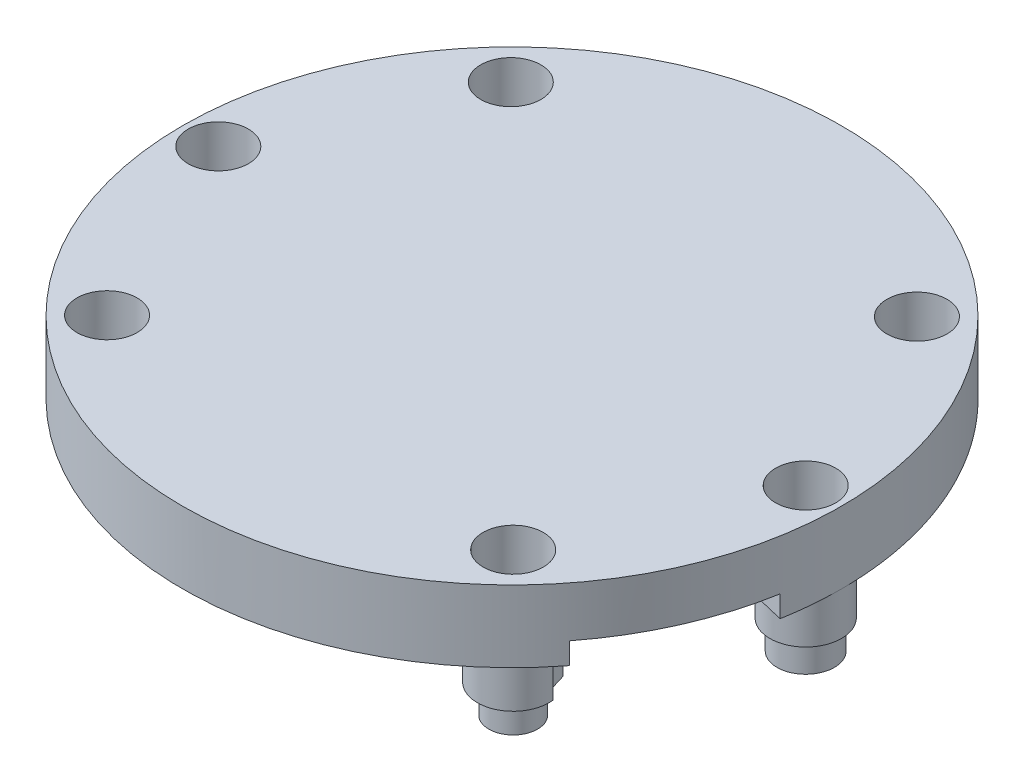
SolidWorks part; units mm, degrees
ref_plane "前视基准面" through (0, 0, 0) normal (0, 0, 1) x (1, 0, 0)
ref_plane "上视基准面" through (0, 0, 0) normal (0, 1, 0) x (1, 0, 0)
ref_plane "右视基准面" through (0, 0, 0) normal (1, 0, 0) x (0, 0, -1)
sketch "草图1" plane through (0, 0, 0) normal (0, 1, 0) x (1, 0, 0)
  line L0 (68.5071, 0) -> (-51.1381, 0) construction
  circle A0 centre (0, 0) radius 23
  circle A1 centre (-20.5, 0) radius 1.05
  circle A2 centre (20.5, 0) radius 1.05
  circle A3 centre (-14.175, 14.0906) radius 1.05
  circle A4 centre (14.1739, 14.0906) radius 1.05
  circle A5 centre (14.1739, -14.0907) radius 1.05
  circle A6 centre (-14.175, -14.0907) radius 1.05
  dimension "D1" = 46
  dimension "D2" = 2.1
  dimension "D3" = 2.1
  dimension "D6" = 2.1
  dimension "D7" = 2.1
  dimension "D10" = 28.1813
  dimension "D4" = 41
  dimension "D5" = 20.5
  dimension "D8" = 28.3489
  dimension "D9" = 14.175
extrude "凸台-拉伸1" add sketch "草图1" along normal blind 5
sketch "草图2" plane through (0, 0, 0) normal (0, -1, 0) x (1, 0, 0)
  circle A0 centre (-14.175, 14.0907) radius 2.5
  circle A1 centre (-20.5, 0) radius 2.5
  circle A3 centre (14.1739, 14.0907) radius 2.5
  circle A4 centre (20.5, 0) radius 2.5
  circle A5 centre (14.1739, -14.0906) radius 2.5
  circle A6 centre (-14.175, -14.0906) radius 2.5
  dimension "D1" = 5
extrude "凸台-拉伸2" add sketch "草图2" along normal blind 5
sketch "草图3" plane through (0, 5, 0) normal (0, 1, 0) x (1, 0, 0)
  circle A0 centre (-14.175, 14.0906) radius 2.1
  circle A1 centre (14.1739, 14.0906) radius 2.1
  circle A2 centre (20.5, 0) radius 2.1
  circle A3 centre (14.1739, -14.0907) radius 2.1
  circle A4 centre (-14.175, -14.0907) radius 2.1
  circle A5 centre (-20.5, 0) radius 2.1
  dimension "D1" = 4.2
extrude "切除-拉伸1" cut sketch "草图3" against normal blind 4
sketch "草图4" plane through (0, 5, 0) normal (0, 1, 0) x (1, 0, 0)
  circle A0 centre (-14.175, 14.0906) radius 1.125
  circle A1 centre (14.1739, 14.0906) radius 1.125
  circle A2 centre (20.5, 0) radius 1.125
  circle A3 centre (14.1739, -14.0907) radius 1.125
  circle A4 centre (-14.175, -14.0907) radius 1.125
  circle A5 centre (-20.5, 0) radius 1.125
  dimension "D1" = 2.25
extrude "切除-拉伸2" cut sketch "草图4" against normal blind 15
sketch "草图5" plane through (0, -5, 0) normal (0, -1, 0) x (1, 0, 0)
  circle A0 centre (-14.175, 14.0907) radius 1.6
  circle A1 centre (-14.175, 14.0907) radius 2.5
  dimension "D1" = 3.2
extrude "切除-拉伸8" cut sketch "草图5" against normal blind 2
sketch "草图6" plane through (0, -5, 0) normal (0, -1, 0) x (1, 0, 0)
  circle A0 centre (-20.5, 0) radius 1.8
  circle A1 centre (-20.5, 0) radius 2.5
  dimension "D1" = 3.6
extrude "切除-拉伸9" cut sketch "草图6" against normal blind 2
sketch "草图7" plane through (0, -5, 0) normal (0, -1, 0) x (-1, 0, 0)
  circle A0 centre (14.175, 14.0906) radius 2
  circle A1 centre (14.175, 14.0906) radius 2.5
  dimension "D1" = 4
extrude "切除-拉伸10" cut sketch "草图7" against normal blind 2
sketch "草图8" plane through (0, -5, 0) normal (0, -1, 0) x (1, 0, 0)
  circle A0 centre (14.1739, -14.0906) radius 1.6
  circle A1 centre (14.1739, -14.0906) radius 2.5
  dimension "D1" = 3.2
extrude "切除-拉伸11" cut sketch "草图8" against normal blind 2
sketch "草图9" plane through (0, -5, 0) normal (0, -1, 0) x (1, 0, 0)
  circle A0 centre (20.5, 0) radius 2
  circle A1 centre (20.5, 0) radius 2.5
  dimension "D1" = 4
extrude "切除-拉伸12" cut sketch "草图9" against normal blind 2
sketch "草图10" plane through (0, -5, 0) normal (0, -1, 0) x (1, 0, 0)
  circle A0 centre (14.1739, 14.0907) radius 1.7
  circle A1 centre (14.1739, 14.0907) radius 2.5
  dimension "D1" = 3.4
extrude "切除-拉伸13" cut sketch "草图10" against normal blind 2
sketch "草图11" plane through (0, -5, 0) normal (0, -1, 0) x (1, 0, 0)
  line L0 (12.6085, -14.9966) -> (14.5924, -14.9966)
  line L1 (14.5924, -14.9966) -> (14.8509, -15.6672)
  line L2 (14.8509, -15.6672) -> (14.1075, -16.134)
  line L4 (14.1075, -16.134) -> (12.6085, -14.9966)
extrude "切除-拉伸16" cut sketch "草图11" against normal blind 2
sketch "草图12" plane through (0, -3, 0) normal (0, -1, 0) x (1, 0, 0)
  line L0 (-16.5326, 13.2589) -> (-12.3563, 11.6712)
  line L1 (-12.3563, 11.6712) -> (-12.9329, 10.1545)
  line L2 (-12.9329, 10.1545) -> (-17.7808, 12.3709)
  line L3 (-17.7808, 12.3709) -> (-16.5326, 13.2589)
  circle A0 centre (-14.175, 14.0907) radius 2.5 construction
extrude "切除-拉伸17" cut sketch "草图12" against normal blind 3
sketch "草图14" plane through (0, -3, 0) normal (0, -1, 0) x (1, 0, 0)
  line L0 (16.1147, 13.7926) -> (15.4507, 11.6284)
  line L1 (15.4507, 11.6284) -> (16.3115, 11.1857)
  line L2 (16.3115, 11.1857) -> (17.5166, 13.7926)
  line L3 (17.5166, 13.7926) -> (16.1147, 13.7926)
extrude "切除-拉伸19" cut sketch "草图14" against normal blind 3
sketch "草图15" plane through (0, 0, 0) normal (0, -1, 0) x (1, 0, 0)
  line L0 (-22.2414, 5.8583) -> (-16.3167, 3.4046)
  line L1 (-16.3167, 3.4046) -> (-12.2221, 11.3712)
  line L2 (-12.2221, 11.3712) -> (-18.1782, 14.0909)
  line L3 (-18.1782, 14.0909) -> (-20.4212, 14.1949)
  line L4 (-20.4212, 14.1949) -> (-22.2414, 8.1222)
  line L5 (-22.2414, 8.1222) -> (-22.2414, 5.8583)
  arc A0 (23, 0) -> (-23, 0) centre (0, 0) ccw construction
extrude "切除-拉伸20" cut sketch "草图15" against normal blind 1.5
sketch "草图16" plane through (0, 0, 0) normal (0, -1, 0) x (1, 0, 0)
  line L2 (20.7665, 15.1771) -> (16.3241, 13.3901)
  line L3 (16.3241, 13.3901) -> (15.8423, 12.6519)
  line L4 (15.8423, 12.6519) -> (15.8148, 12.3148)
  line L5 (15.8148, 12.3148) -> (18.998, 3.0719)
  line L6 (18.998, 3.0719) -> (24.148, 4.3014)
  line L7 (24.148, 4.3014) -> (20.7665, 15.1771)
extrude "切除-拉伸21" cut sketch "草图16" against normal blind 1.5
